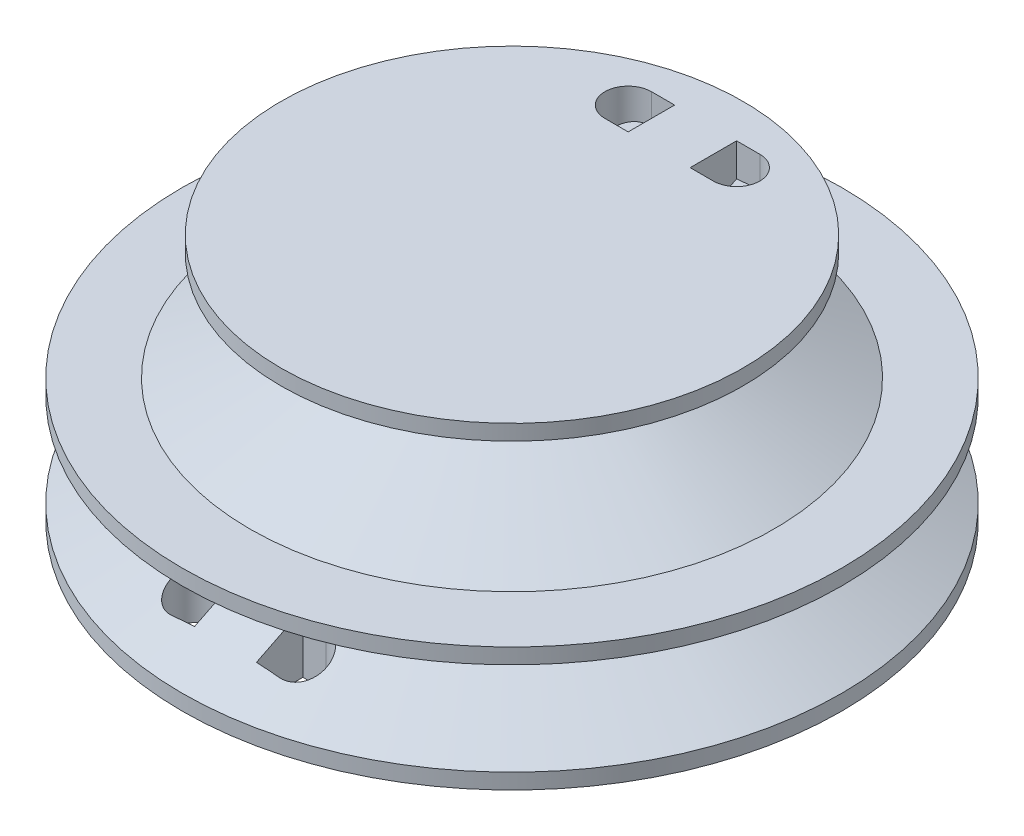
SolidWorks part; units mm, degrees
ref_plane "Front Plane" through (0, 0, 0) normal (0, 0, 1) x (1, 0, 0)
ref_plane "Top Plane" through (0, 0, 0) normal (0, 1, 0) x (1, 0, 0)
ref_plane "Right Plane" through (0, 0, 0) normal (1, 0, 0) x (0, 0, -1)
sketch "24" plane through (0, 0, 0) normal (0, 1, 0) x (1, 0, 0)
  circle A0 centre (0, 0) radius 7.6433
  dimension "D1" = 15.2866
extrude "Boss-Extrude1" add sketch "24" along normal blind 4
sketch "Sketch3" plane through (0, 0, 0) normal (0, 0, 1) x (1, 0, 0)
  line L0 (-7.6433, 4) -> (-10.6433, 4)
  line L1 (-10.6433, 4) -> (-10.6433, 3.5)
  line L2 (-10.6433, 3.5) -> (-7.6433, 2)
  line L3 (-7.6433, 4) -> (-7.6433, 0) construction
  line L4 (-7.6433, 2) -> (-10.6433, 0.5)
  line L5 (-10.6433, 0.5) -> (-10.6433, 0)
  line L6 (-7.6433, 4) -> (-7.6433, 0)
  line L7 (-10.6433, 0) -> (-7.6433, 0)
  dimension "D1" = 3
  dimension "D2" = 0.5
sketch "Sketch4" plane through (0, 0, 0) normal (1, 0, 0) x (0, 0, -1)
  line L0 (0, 4) -> (0, 0) construction
  line L1 (7.6433, 4) -> (-7.6433, 4) construction
revolve "Revolve1" add sketch "Sketch3" angle 360 about L0 region at (-8.8433, 3.3, 0) region at (-8.8433, 0.7, 0)
sketch "Sketch5" plane through (0, 4, 0) normal (0, 1, 0) x (1, 0, 0)
  circle A0 centre (0, 0) radius 4.4586
  dimension "D1" = 8.9172
extrude "Boss-Extrude2" add sketch "Sketch5" along normal blind 4
sketch "Sketch6" plane through (0, 0, 0) normal (0, 0, 1) x (1, 0, 0)
  line L0 (-4.4586, 8) -> (-7.4586, 8)
  line L1 (-7.4586, 8) -> (-7.4586, 7.5)
  line L2 (-7.4586, 7.5) -> (-4.4586, 6)
  line L4 (-4.4586, 6) -> (-7.4586, 4.5)
  line L6 (10.6433, 4) -> (-10.6433, 4) construction
  line L7 (-7.4586, 4) -> (-4.4586, 4)
  line L8 (-4.4586, 8) -> (-4.4586, 4) construction
  line L9 (-4.4586, 8) -> (-4.4586, 4)
  line L10 (-7.4586, 4.5) -> (-8.4586, 4)
  line L11 (-8.4586, 4) -> (-7.4586, 4)
  line L12 (-7.4586, 4.5) -> (-7.4586, 4) construction
  dimension "D1" = 3
  dimension "D2" = 0.5
revolve "Revolve2" add sketch "Sketch6" angle 360 about L0 region at (-5.6586, 7.3, 0) region at (-5.6586, 4.7, 0) region at (-7.7919, 4.1667, 0)
sketch "Sketch8" plane through (0, 0, 0) normal (0, -1, 0) x (1, 0, 0)
  line L0 (-1.75, 8.5) -> (1.75, 8.5) construction
  line L1 (-1.75, 9.25) -> (1.75, 9.25)
  line L2 (-1.75, 7.75) -> (1.75, 7.75)
  line L3 (0, 8.5) -> (0, 0) construction
  line L4 (0, 9.25) -> (0, 7.75) construction
  line L5 (-1, 9.25) -> (-1, 7.75)
  line L6 (1, 9.25) -> (1, 7.75)
  arc A0 (-1.75, 9.25) -> (-1.75, 7.75) centre (-1.75, 8.5) ccw
  arc A1 (1.75, 7.75) -> (1.75, 9.25) centre (1.75, 8.5) ccw
  circle A2 centre (0, 0) radius 10.6433 construction
  point P2 (0, 8.5)
  point P7 (2.5, 8.5)
  point P8 (-2.5, 8.5)
  dimension "D1" = 1.5
  dimension "D2" = 5
  dimension "D3" = 8.5
  dimension "D4" = 1
  dimension "D5" = 1
extrude "Cut-Extrude2" cut sketch "Sketch8" against normal blind 2 contours L1 A0 L2 L5 | L2 A1 L1 L6 region at (-1.68, 0, 8.5) region at (1.68, 0, 8.5)
sketch "Sketch9" plane through (0, 8, -8) normal (0, -1, 0) x (-1, 0, 0)
  line L0 (-1.75, -2.5) -> (1.75, -2.5) construction
  line L1 (-1.75, -1.75) -> (1.75, -1.75)
  line L2 (-1.75, -3.25) -> (1.75, -3.25)
  line L3 (0, -2.5) -> (0, -8) construction
  line L4 (0, -1.75) -> (0, -3.25) construction
  line L5 (-1, -1.75) -> (-1, -3.25)
  line L6 (1, -1.75) -> (1, -3.25)
  arc A0 (-1.75, -1.75) -> (-1.75, -3.25) centre (-1.75, -2.5) ccw
  arc A1 (1.75, -3.25) -> (1.75, -1.75) centre (1.75, -2.5) ccw
  point P2 (0, -2.5)
  point P7 (2.5, -2.5)
  point P8 (-2.5, -2.5)
  dimension "D1" = 1.5
  dimension "D2" = 5
  dimension "D3" = 5.5
  dimension "D4" = 1
  dimension "D5" = 1
extrude "Cut-Extrude3" cut sketch "Sketch9" along normal blind 2 contours A0 L1 L5 L2 | A1 L2 L6 L1 region at (1.68, 8, -5.5) region at (-1.68, 8, -5.5)
